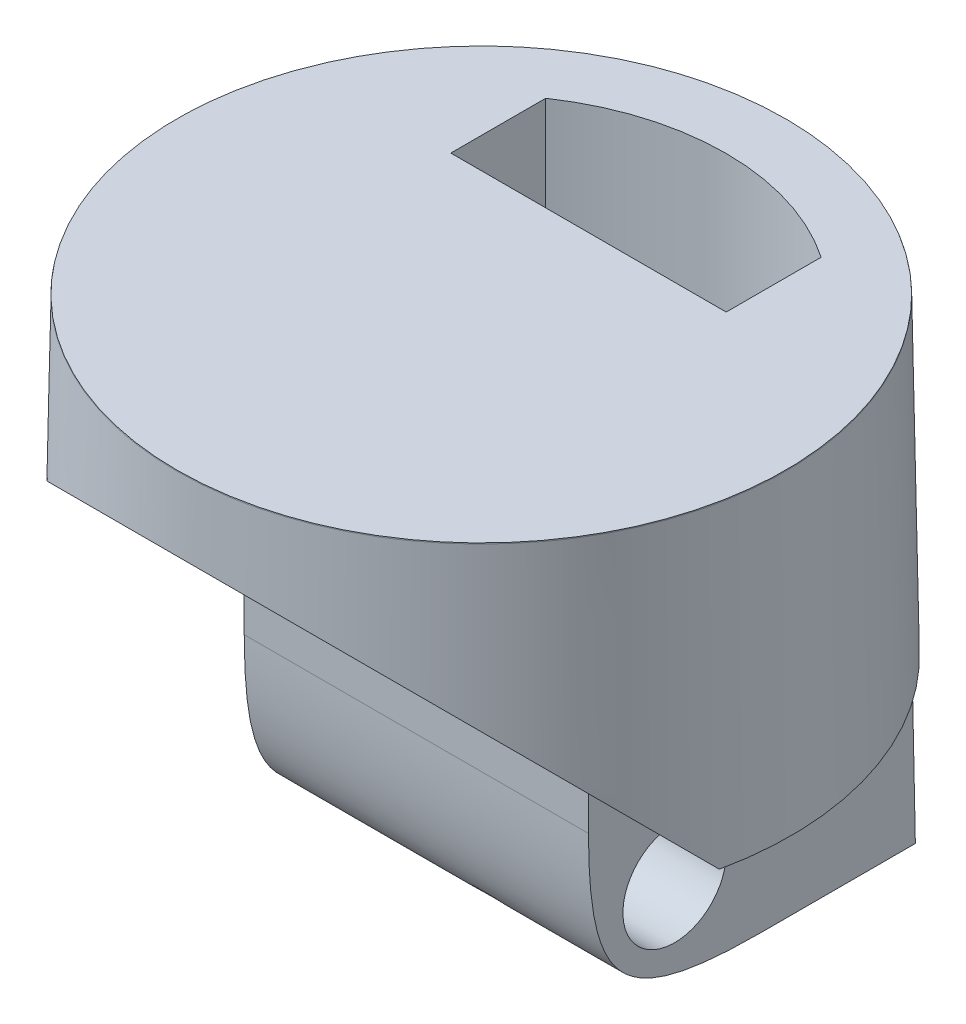
SolidWorks part; units mm, degrees
ref_plane "Front Plane" through (0, 0, 0) normal (0, 0, 1) x (1, 0, 0)
ref_plane "Top Plane" through (0, 0, 0) normal (0, 1, 0) x (1, 0, 0)
ref_plane "Right Plane" through (0, 0, 0) normal (1, 0, 0) x (0, 0, -1)
sketch "Sketch1" plane through (0, 0, 0) normal (0, 1, 0) x (1, 0, 0)
  circle A0 centre (0, 0) radius 9
  dimension "D1" = 18
extrude "Boss-Extrude1" add sketch "Sketch1" along normal blind 19 draft 1 and the other way blind 6 draft 1
sketch "Sketch3" plane through (0, 0, 0) normal (1, 0, 0) x (0, 0, -1)
  line L0 (-1.8929, -0.1305) -> (-1.8929, -6.1305) construction
  line L1 (-1.8861, -6) -> (-1.8861, 0)
  line L2 (-9.1047, -6) -> (9.1047, -6) construction
  line L3 (-1.8861, 0) -> (-9.9298, 8.0437)
  line L4 (-9.9298, 8.0437) -> (-9.9298, -6)
  line L5 (-9.9298, -6) -> (-1.8861, -6)
  dimension "D1" = 6
  dimension "D2" = 135
  dimension "D3" = 6
extrude "Cut-Extrude1" cut sketch "Sketch3" against normal through all both and the other way through all
sketch "Sketch4" plane through (0, 0, 1.8861) normal (0, 0, 1) x (1, 0, 0)
  line L0 (8.9072, -6) -> (-8.9072, -6) construction
  line L1 (-5, -6) -> (5, -6)
  line L2 (-5, -6) -> (-5, 0)
  line L3 (-5, 0) -> (5, 0)
  line L4 (5, -6) -> (5, 0)
  line L5 (-5, -6) -> (5, 0) construction
  line L6 (-5, 0) -> (5, -6) construction
  line L8 (-11.5027, -6) -> (11.5027, -6)
  line L9 (-11.5027, -6) -> (-11.5027, 0)
  line L10 (-11.5027, 0) -> (11.5027, 0)
  line L11 (11.5027, -6) -> (11.5027, 0)
  line L12 (-11.5027, -6) -> (11.5027, 0) construction
  line L13 (-11.5027, 0) -> (11.5027, -6) construction
  point P0 (0, -3)
  point P9 (0, -3)
  dimension "D1" = 6
  dimension "D2" = 10
extrude "Cut-Extrude2" cut sketch "Sketch4" against normal through all
sketch "Sketch5" plane through (5, 0, 0) normal (1, 0, 0) x (0, 0, -1)
  line L0 (7.6089, -6) -> (-1.8861, -6) construction
  line L1 (-1.8861, -6) -> (-1.8861, 0) construction
  circle A0 centre (0.6139, -3.5) radius 1.5
  dimension "D3" = 3
  dimension "D1" = 2.5
  dimension "D2" = 2.5
extrude "Cut-Extrude3" cut sketch "Sketch5" against normal through all
fillet "Fillet1" radius 5 1 edges at (0, -6, 1.8861)
fillet "Fillet2" radius 10 1 edges at (0, 19, 8.6684)
sketch "Sketch6" plane through (0, 0, 0) normal (1, 0, 0) x (0, 0, -1)
  line L1 (-10.4929, 20) -> (14.2014, 20)
  line L2 (-10.4929, 20) -> (-10.4929, 9.1165)
  line L3 (-10.4929, 9.1165) -> (14.2014, 9.1165)
  line L4 (14.2014, 20) -> (14.2014, 9.1165)
extrude "Cut-Extrude4" cut sketch "Sketch6" against normal through all both and the other way through all
sketch "Sketch7" plane through (0, -6, 0) normal (0, -1, 0) x (1, 0, 0)
  line L6 (4, -3.1139) -> (4, -5.8717)
  line L7 (5, -3.1139) -> (-5, -3.1139) construction
  line L8 (4, -3.1139) -> (-4, -3.1139)
  line L9 (-4, -3.1139) -> (-4, -5.8717)
  line L11 (-5, -7.6089) -> (-5, -3.1139) construction
  line L12 (5, -7.6089) -> (5, -3.1139) construction
  arc A6 (-3.9017, -5.9375) -> (3.9017, -5.9375) centre (0, 0) ccw
  arc A7 (-4, -5.8717) -> (4, -5.8717) centre (0, 0) ccw
  dimension "D2" = 1
  dimension "D3" = 1
  dimension "D1" = 2
extrude "Cut-Extrude5" cut sketch "Sketch7" against normal through all
